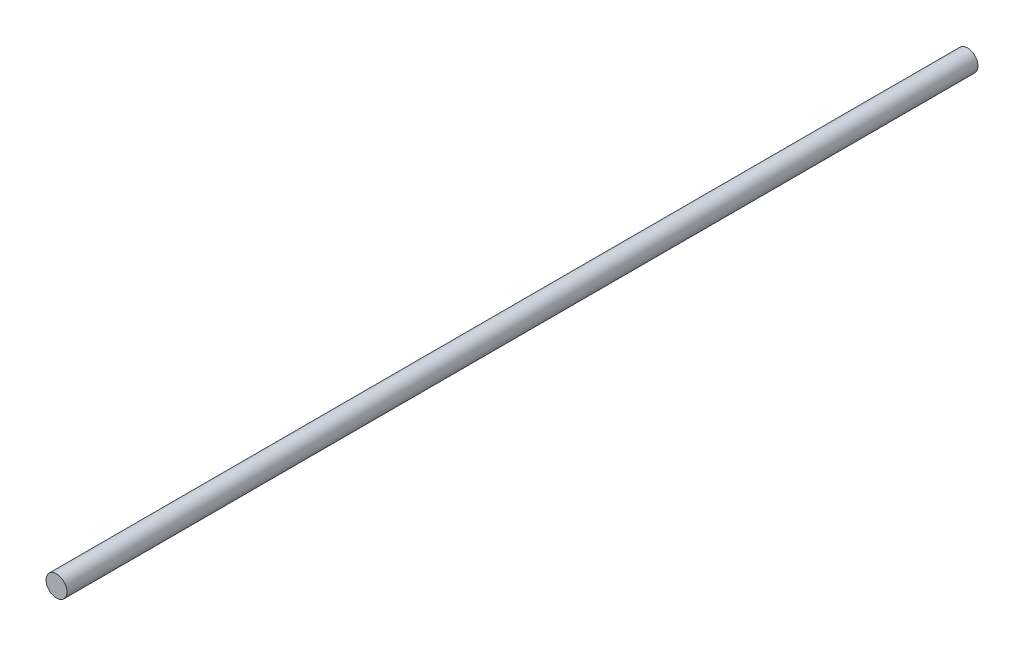
SolidWorks part; units mm, degrees
material "AISI 304"
ref_plane "Front Plane" through (0, 0, 0) normal (0, 0, 1) x (1, 0, 0)
ref_plane "Top Plane" through (0, 0, 0) normal (0, 1, 0) x (1, 0, 0)
ref_plane "Right Plane" through (0, 0, 0) normal (1, 0, 0) x (0, 0, -1)
sketch "Sketch1" plane through (0, 0, 0) normal (0, 0, 1) x (1, 0, 0)
  circle A0 centre (0, 0) radius 1.5
  dimension "D1" = 3
extrude "Boss-Extrude1" add sketch "Sketch1" along normal mid plane 130
